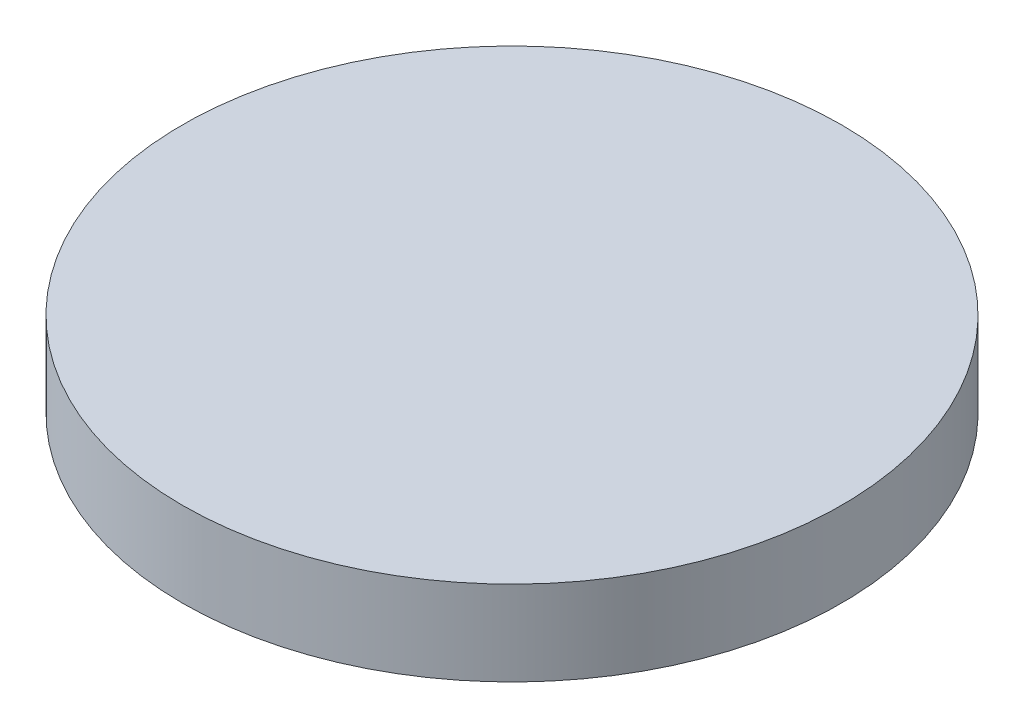
SolidWorks part; units mm, degrees
note: '?' marks a value the reader was unsure of. The reader was unsure of these and kept them because the rebuilt part matched: shared geometry of "Sketch3<4>".
ref_plane "Front Plane" through (0, 0, 0) normal (0, 0, 1) x (1, 0, 0)
ref_plane "Top Plane" through (0, 0, 0) normal (0, 1, 0) x (1, 0, 0)
ref_plane "Right Plane" through (0, 0, 0) normal (1, 0, 0) x (0, 0, -1)
sketch "Sketch1" plane through (0, 0, 0) normal (0, 1, 0) x (1, 0, 0)
  circle A0 centre (0, 0) radius 17.5
extrude "Boss-Extrude1" add sketch "Sketch1" along normal blind 1.5
sketch "Sketch3" plane through (0, 0, 0) normal (0, -1, 0) x (1, 0, 0)
  line L0 (0, -17.5) -> (0, 17.5)
  line L1 (17.5, 0) -> (-17.5, 0)
  line L3 (0, 15) -> (0.5, 15)
  line L4 (0, 15) -> (0, 16.5)
  line L5 (0, 16.5) -> (0.5, 16.5)
  line L6 (0.5, 15) -> (0.5, 16.5)
  line L7 (0.5, 16.5) -> (-0.5, 16.5)
  line L8 (0.5, 16.5) -> (0.5, 15)
  line L9 (0.5, 15) -> (-0.5, 15)
  line L10 (-0.5, 16.5) -> (-0.5, 15)
  circle A0 centre (0, 0) radius 15
  circle A1 centre (0, 0) radius 17.5 construction
  circle A2 centre (0, 0) radius 16.5
  point P3 (0, 15)
  point P8 (0, 0)
  point P11 (0, 0)
extrude "Boss-Extrude3" add sketch "Sketch3" along normal blind 0.5 contours L7 L10 L9 L8
extrude "Boss-Extrude4" add sketch "Sketch3<4>" along normal blind 3 contours A2 L10 L7 L0 L1 | A2 L1 L0 L5 L8 | A2 L1 L0 | A2 L0 L1
sketch "Sketch3<4>" plane through (0, 0, 0) normal (0, -1, 0) x (1, 0, 0) same geometry as "Sketch3"
sketch "Sketch4" plane through (0, -3, 0) normal (0, -1, 0) x (1, 0, 0)
  line L0 (-0.5, 16.4924) -> (-0.5, 16.49)
  line L2 (-0.5, 16.49) -> (0.5, 16.49)
  line L3 (-0.5, 16.49) -> (-0.5, 16.5)
  line L4 (-0.5, 16.5) -> (0.5, 16.5)
  line L5 (0.5, 16.49) -> (0.5, 16.5)
  circle A0 centre (0, 0) radius 16.5
  line M6 (0.5, 16.5) -> (0.5, 16.4924)
  line M8 (-0.5, 16.4924) -> (-0.5, 16.5)
  line M9 (-0.5, 16.5) -> (0.5, 16.5)
extrude "Boss-Extrude6" add sketch "Sketch4" against normal blind 2.5 contours A0 M9 M8 | A0 L4 M6
ref_axis "Axis1" through (0, -3, 0) along (0, 1, 0)?
ref_plane "Plane3" through (0, 0, 0) normal (0, 0, -1) x (-1, 0, 0)
split "Split2" trim tools "Plane3" bodies to split 107 resulting bodies 109
mirror "Mirror1" about plane through (0, 0, 0) normal (0, 0, -1) of bodies 109
ref_plane "Plane4" through (0, 0, 0) normal (-1, 0, 0) x (0, 1, 0)
move or copy body "Body-Move/Copy1" bodies to move or copy 110 copy yes number of copies 1 rotation origin (0, 0, 0) rotation axis (0, 1, 0) rotation angle 90
combine bodies "Combine1" operation type add bodies to combine 110 112
